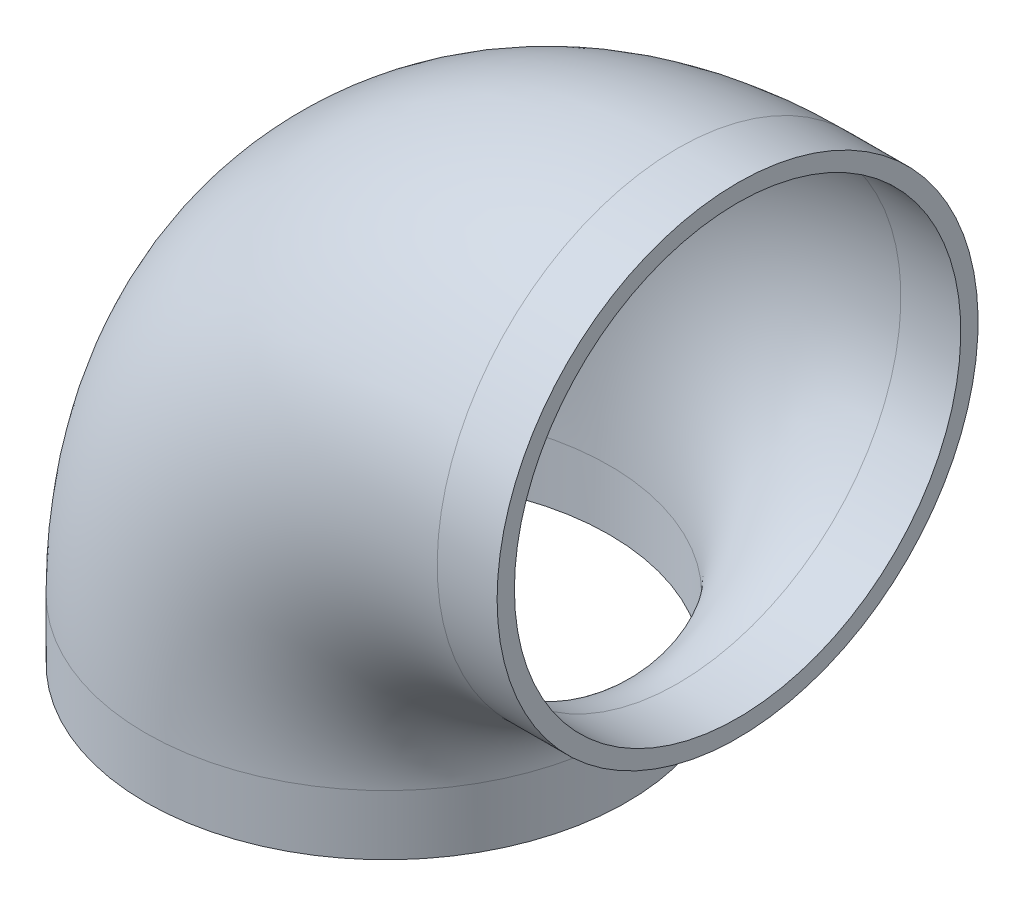
SolidWorks part; units mm, degrees
material "PVC Rígido"
ref_plane "Alzado" through (0, 0, 0) normal (0, 0, 1) x (1, 0, 0)
ref_plane "Planta" through (0, 0, 0) normal (0, 1, 0) x (1, 0, 0)
ref_plane "Vista lateral" through (0, 0, 0) normal (1, 0, 0) x (0, 0, -1)
sketch "Croquis2" plane through (0, 0, 0) normal (0, 0, 1) x (1, 0, 0)
  line L0 (0, 0) -> (0, 27.27)
  line L1 (132.73, 160) -> (160, 160)
  arc A0 (0, 27.27) -> (132.73, 160) centre (132.73, 27.27) cw
  point P6 (0, 160)
  point P9 (0, 160)
  dimension "D3" = 132.73
  dimension "D1" = 160
  dimension "D2" = 160
sketch "Croquis3" plane through (0, 0, 0) normal (0, 1, 0) x (1, 0, 0)
  circle A0 centre (0, 0) radius 109.474
  circle A1 centre (0, 0) radius 101.6
  dimension "D1" = 218.948
  dimension "D2" = 203.2
sweep "Barrer1" add profiles "Croquis3" path "Croquis2"
sketch "Croquis4" plane through (160, 0, 0) normal (1, 0, 0) x (0, 0, -1)
  circle A0 centre (0, 160) radius 119.474
  circle A1 centre (0, 160) radius 109.474
  circle A2 centre (0, 160) radius 109.474
  dimension "D2" = 10
  dimension "D1" = 0
sketch "Croquis5" plane through (0, 0, 0) normal (0, -1, 0) x (1, 0, 0)
  circle A0 centre (0, 0) radius 119.474
  circle A1 centre (0, 0) radius 109.474
  circle A2 centre (0, 0) radius 109.474
  dimension "D2" = 10
  dimension "D1" = 0
